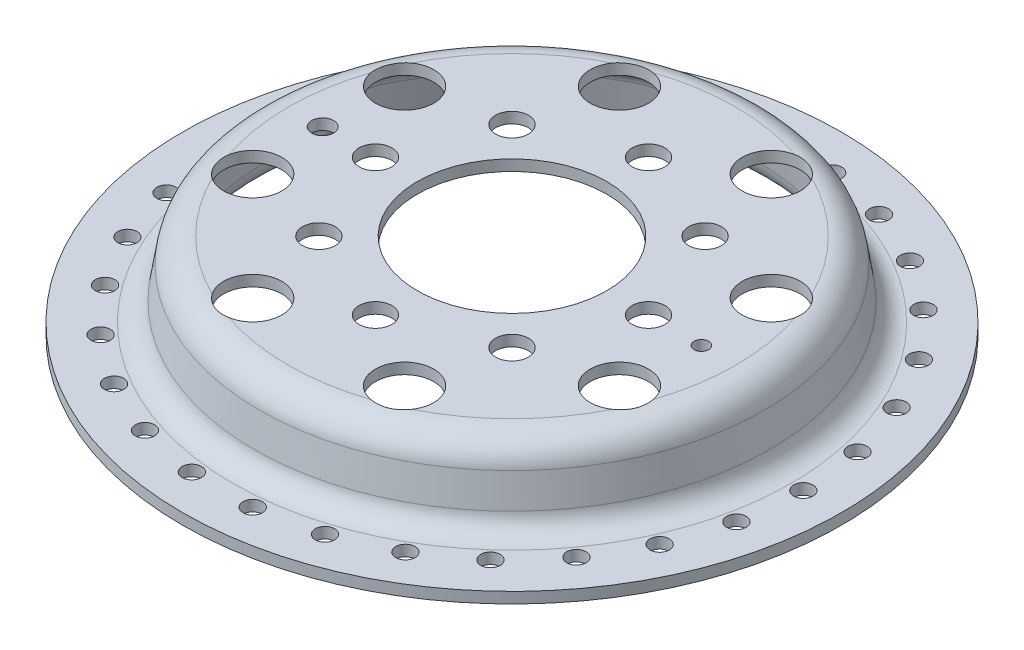
SolidWorks part; units mm, degrees
ref_plane "Plano frontal" through (0, 0, 0) normal (0, 0, 1) x (1, 0, 0)
ref_plane "Plano superior" through (0, 0, 0) normal (0, 1, 0) x (1, 0, 0)
ref_plane "Plano direito" through (0, 0, 0) normal (1, 0, 0) x (0, 0, -1)
sketch "Esboço1" plane through (0, 0, 0) normal (0, 0, 1) x (1, 0, 0)
  line L0 (0, -45.0344) -> (0, 42.8268) construction
  line L1 (26, 19.4266) -> (68.2531, 19.4266)
  line L2 (90.5, -4.0734) -> (68.5, -4.0734)
  line L3 (68.5, -4.0734) -> (65.2531, 16.4266)
  line L4 (65.2531, 16.4266) -> (26, 16.4266)
  line L5 (26, 16.4266) -> (26, 19.4266)
  line L6 (68.2531, 19.4266) -> (71.5, -1.0734)
  line L7 (71.5, -1.0734) -> (90.5, -1.0734)
  line L8 (90.5, -1.0734) -> (90.5, -4.0734)
  line L9 (90.5, -4.0734) -> (90.7208, -4.0734)
  dimension "D1" = 26
  dimension "D2" = 9
  dimension "D3" = 90.5
  dimension "D4" = 71.5
  dimension "D5" = 68.5
  dimension "D6" = 3
  dimension "D7" = 3
  dimension "D8" = 23.5
revolve "Revolução3" add sketch "Esboço1" angle 360 about L0
sketch "Esboço2" plane through (0, 19.4266, 0) normal (0, 1, 0) x (1, 0, 0)
  line L0 (-68.2531, 0) -> (68.2531, 0) construction
  circle A0 centre (0, 0) radius 68.2531 construction
  circle A1 centre (0, 0) radius 37.5 construction
  circle A2 centre (-37.5, 0) radius 4.5
  circle A3 centre (-26.5165, 26.5165) radius 4.5
  circle A4 centre (0, 37.5) radius 4.5
  circle A5 centre (26.5165, 26.5165) radius 4.5
  circle A6 centre (37.5, 0) radius 4.5
  circle A7 centre (26.5165, -26.5165) radius 4.5
  circle A8 centre (0, -37.5) radius 4.5
  circle A9 centre (-26.5165, -26.5165) radius 4.5
  dimension "D1" = 75
  dimension "D2" = 9
  dimension "D3" = 8
extrude "Corte-extrusão1" cut sketch "Esboço2" against normal blind 10
sketch "Esboço3" plane through (0, 19.4266, 0) normal (0, 1, 0) x (1, 0, 0)
  line L0 (-68.2531, 0) -> (68.2531, 0) construction
  circle A0 centre (0, 0) radius 68.2531 construction
  circle A1 centre (0, 0) radius 54.5 construction
  circle A3 centre (-50.3514, 20.8562) radius 8
  circle A5 centre (-20.8562, 50.3514) radius 8
  circle A7 centre (20.8562, 50.3514) radius 8
  circle A9 centre (50.3514, 20.8562) radius 8
  circle A11 centre (50.3514, -20.8562) radius 8
  circle A13 centre (20.8562, -50.3514) radius 8
  circle A15 centre (-20.8562, -50.3514) radius 8
  circle A17 centre (-50.3514, -20.8562) radius 8
  dimension "D1" = 109
extrude "Corte-extrusão2" cut sketch "Esboço3" against normal blind 10
sketch "Esboço4" plane through (0, 19.4266, 0) normal (0, 1, 0) x (1, 0, 0)
  circle A0 centre (0, 0) radius 52 construction
  circle A1 centre (-52, 0) radius 3
  circle A2 centre (52, 0) radius 2
  dimension "D1" = 104
  dimension "D2" = 6
  dimension "D3" = 4
extrude "Corte-extrusão3" cut sketch "Esboço4" against normal blind 10
sketch "Esboço5" plane through (0, -1.0734, 0) normal (0, 1, 0) x (1, 0, 0)
  circle A0 centre (0, 0) radius 80 construction
  circle A1 centre (-80, 0) radius 2.65
  circle A2 centre (-78.2518, 16.6329) radius 2.65
  circle A3 centre (-73.0836, 32.5389) radius 2.65
  circle A4 centre (-64.7214, 47.0228) radius 2.65
  circle A5 centre (-53.5304, 59.4516) radius 2.65
  circle A6 centre (-40, 69.282) radius 2.65
  circle A7 centre (-24.7214, 76.0845) radius 2.65
  circle A8 centre (-8.3623, 79.5618) radius 2.65
  circle A9 centre (8.3623, 79.5618) radius 2.65
  circle A10 centre (24.7214, 76.0845) radius 2.65
  circle A11 centre (40, 69.282) radius 2.65
  circle A12 centre (53.5304, 59.4516) radius 2.65
  circle A13 centre (64.7214, 47.0228) radius 2.65
  circle A14 centre (73.0836, 32.5389) radius 2.65
  circle A15 centre (78.2518, 16.6329) radius 2.65
  circle A16 centre (80, 0) radius 2.65
  circle A17 centre (78.2518, -16.6329) radius 2.65
  circle A18 centre (73.0836, -32.5389) radius 2.65
  circle A19 centre (64.7214, -47.0228) radius 2.65
  circle A20 centre (53.5304, -59.4516) radius 2.65
  circle A21 centre (40, -69.282) radius 2.65
  circle A22 centre (24.7214, -76.0845) radius 2.65
  circle A23 centre (8.3623, -79.5618) radius 2.65
  circle A24 centre (-8.3623, -79.5618) radius 2.65
  circle A25 centre (-24.7214, -76.0845) radius 2.65
  circle A26 centre (-40, -69.282) radius 2.65
  circle A27 centre (-53.5304, -59.4516) radius 2.65
  circle A28 centre (-64.7214, -47.0228) radius 2.65
  circle A29 centre (-73.0836, -32.5389) radius 2.65
  circle A30 centre (-78.2518, -16.6329) radius 2.65
  dimension "D1" = 160
  dimension "D2" = 5.3
  dimension "D3" = 30
extrude "Corte-extrusão4" cut sketch "Esboço5" against normal blind 10
fillet "Filete1" radius 8 1 edges at (0, 19.4266, -68.2531)
fillet "Filete2" radius 6 1 edges at (0, -1.0734, -71.5)
fillet "Filete3" radius 5 1 edges at (0, 16.4266, -65.2531)
fillet "Filete4" radius 9 1 edges at (0, -4.0734, -68.5)
